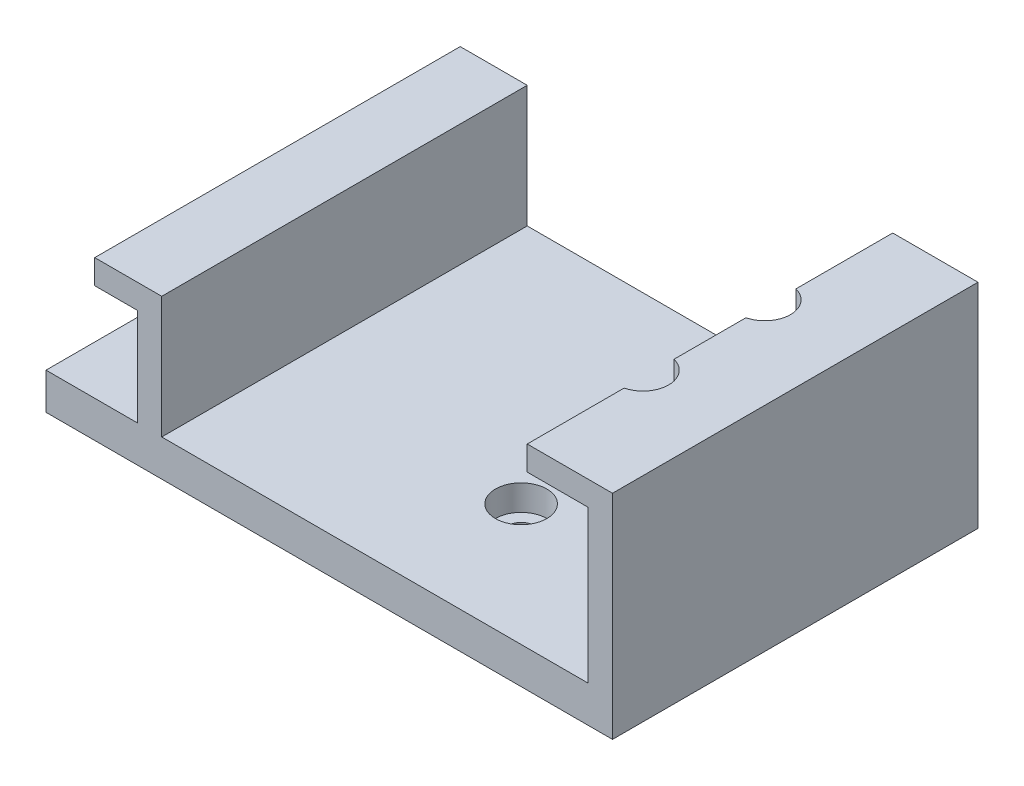
SolidWorks part; units mm, degrees
ref_plane "Front Plane" through (0, 0, 0) normal (0, 0, 1) x (1, 0, 0)
ref_plane "Top Plane" through (0, 0, 0) normal (0, 1, 0) x (1, 0, 0)
ref_plane "Right Plane" through (0, 0, 0) normal (1, 0, 0) x (0, 0, -1)
sketch "Sketch1" plane through (0, 0, 0) normal (0, 0, 1) x (1, 0, 0)
  line L0 (-14, 0) -> (0, 0)
  line L1 (0, 0) -> (0, -35)
  line L2 (0, -35) -> (-93, -35)
  line L3 (-93, -35) -> (-93, -29)
  line L4 (-93, -29) -> (-78, -29)
  line L5 (-78, -29) -> (-78, -13)
  line L6 (-78, -13) -> (-85, -13)
  line L7 (-85, -13) -> (-85, -9)
  line L8 (-85, -9) -> (-74, -9)
  line L9 (-74, -9) -> (-74, -29)
  line L10 (-74, -29) -> (-4, -29)
  line L11 (-4, -29) -> (-4, -4)
  line L12 (-4, -4) -> (-14, -4)
  line L13 (-14, -4) -> (-14, 0)
  dimension "D1" = 25
  dimension "D2" = 70
  dimension "D3" = 6
  dimension "D4" = 6
  dimension "D5" = 4
  dimension "D6" = 4
  dimension "D7" = 4
  dimension "D8" = 4
  dimension "D9" = 10
  dimension "D10" = 16
  dimension "D11" = 7
  dimension "D12" = 15
extrude "Extrude-Base" add sketch "Sketch1" along normal mid plane 60
sketch "Sketch2" plane through (0, -29, 0) normal (0, 1, 0) x (1, 0, 0)
  line L0 (-15, -10) -> (-15, 10) construction
  line L1 (-15, 10) -> (-35, 10) construction
  line L2 (-35, 10) -> (-35, -10) construction
  line L3 (-35, -10) -> (-15, -10) construction
  line L4 (0, -30) -> (0, 30) construction
  line L5 (0, 0) -> (-35, 0) construction
  circle A0 centre (-15, -10) radius 2.2
  circle A1 centre (-15, 10) radius 2.2
  circle A2 centre (-35, 10) radius 2.2
  circle A3 centre (-35, -10) radius 2.2
  point P6 (-15, 0)
  point P9 (0, 0)
  dimension "D4" = 4.4
  dimension "D5" = 4.4
  dimension "D6" = 4.4
  dimension "D7" = 4.4
  dimension "D1" = 15
  dimension "D2" = 20
  dimension "D3" = 20
extrude "Cut-Bolt Holes" cut sketch "Sketch2" against normal blind 10
sketch "Sketch3" plane through (0, -29, 0) normal (0, 1, 0) x (1, 0, 0)
  circle A0 centre (-35, 10) radius 4.215
  circle A1 centre (-15, 10) radius 4.215
  circle A2 centre (-15, -10) radius 4.215
  circle A3 centre (-35, -10) radius 4.215
  circle A4 centre (-35, -10) radius 2.2 construction
  circle A5 centre (-15, -10) radius 2.2 construction
  circle A6 centre (-15, 10) radius 2.2 construction
  circle A7 centre (-35, 10) radius 2.2 construction
  dimension "D1" = 8.43
  dimension "D2" = 8.43
  dimension "D3" = 8.43
  dimension "D4" = 8.43
extrude "Cut-Bolt Head Insets" cut sketch "Sketch3" against normal blind 4.2 and the other way blind 40
sketch "Sketch4" plane through (-93, 0, 0) normal (-1, 0, 0) x (0, 0, 1)
  line L0 (30, -35) -> (-30, -35) construction
  line L1 (20, -35) -> (-20, -35)
  line L2 (20, -35) -> (20, -32)
  line L3 (20, -32) -> (-20, -32)
  line L4 (-20, -35) -> (-20, -32)
  point P7 (0, -35)
  point P8 (0, -35)
  dimension "D1" = 40
  dimension "D2" = 3
extrude "Cut-Top Clearance Slot" cut sketch "Sketch4" against normal blind 45
fillet "Fillet-Clearance Slot Pt 1" radius 3 2 edges at (-70.5, -32, 20) (-70.5, -32, -20)
fillet "Fillet-Clearance Slot Pt 2" radius 3 2 edges at (-70.5, -35, 20) (-70.5, -35, -20)
equation "\"holeBoltDiam\"=4.4"
equation "\"D4@Sketch2\"=\"holeBoltDiam\""
equation "\"D5@Sketch2\"=\"holeBoltDiam\""
equation "\"D6@Sketch2\"=\"holeBoltDiam\""
equation "\"D7@Sketch2\"=\"holeBoltDiam\""
equation "\"insetBoltHead\"=8.43"
equation "\"D1@Sketch3\"=\"insetBoltHead\""
equation "\"D2@Sketch3\"=\"insetBoltHead\""
equation "\"D3@Sketch3\"=\"insetBoltHead\""
equation "\"D4@Sketch3\"=\"insetBoltHead\""
